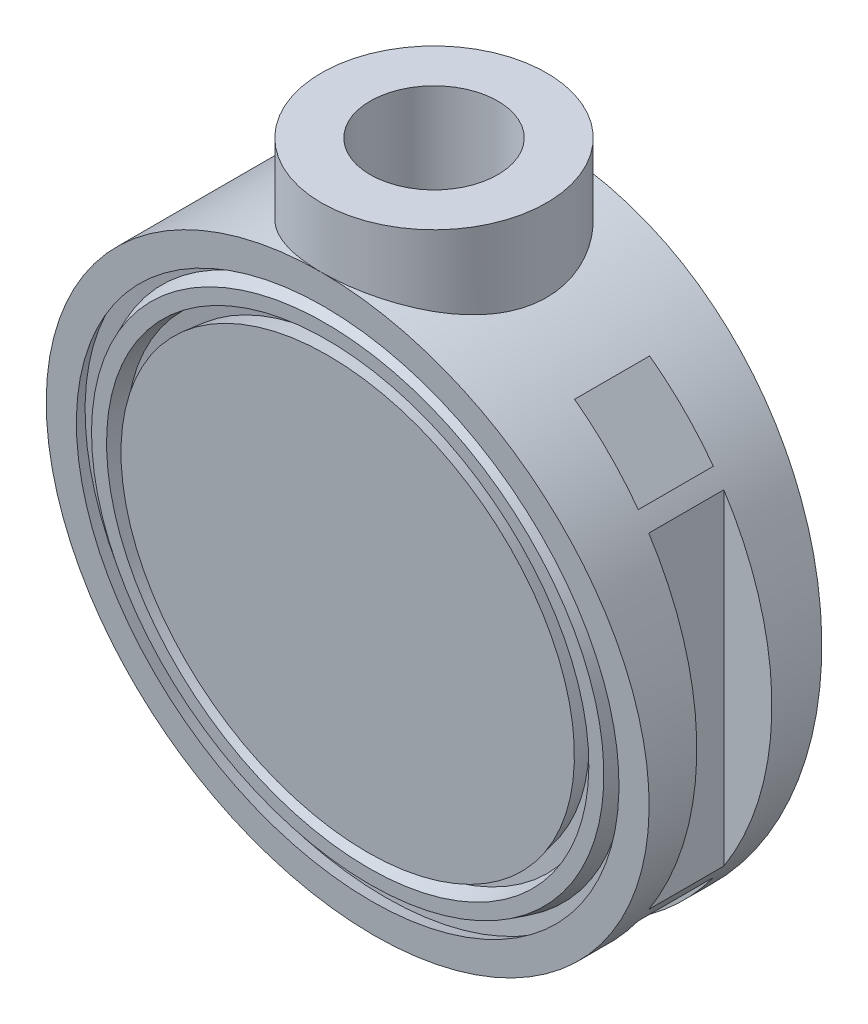
SolidWorks part; units mm, degrees
note: The reader was unsure of these and kept them because the rebuilt part matched: shared geometry of "Sketch3<4>".
ref_plane "Front Plane" through (0, 0, 0) normal (0, 0, 1) x (1, 0, 0)
ref_plane "Top Plane" through (0, 0, 0) normal (0, 1, 0) x (1, 0, 0)
ref_plane "Right Plane" through (0, 0, 0) normal (1, 0, 0) x (0, 0, -1)
sketch "Sketch1" plane through (0, 0, 0) normal (1, 0, 0) x (0, 0, -1)
  line L0 (0, 0) -> (0, 63.5) construction
  line L1 (-23.8125, 63.5) -> (23.8125, 63.5)
  line L2 (23.8125, 63.5) -> (23.8125, 0)
  line L3 (-23.8125, 0) -> (23.8125, 0) construction
  line L4 (-23.8125, 63.5) -> (-23.8125, 0)
  line L5 (-23.8125, 0) -> (23.8125, 0)
  dimension "D1" = 23.8125
  dimension "D2" = 63.5
revolve "Revolve1" add sketch "Sketch1" angle 360 about L5
sketch "Sketch2" plane through (0, 0, 0) normal (1, 0, 0) x (0, 0, -1)
  line L0 (-23.8125, 63.5) -> (-12.7, -63.5)
  line L1 (-23.8125, -63.5) -> (23.8125, -63.5) construction
  line L2 (-12.7, -63.5) -> (0, -63.5)
  line L4 (23.8125, 63.5) -> (-23.8125, 63.5) construction
  line L5 (0, 63.5) -> (0, -63.5) construction
  line L6 (-23.8125, 63.5) -> (-23.8125, -63.5) construction
  line L7 (-23.8125, -63.5) -> (23.8125, -63.5)
  line L8 (-23.8125, 63.5) -> (-23.8125, -63.5)
  line L9 (23.8125, 63.5) -> (23.8125, -63.5)
  line L10 (23.8125, 63.5) -> (12.7, -63.5)
  dimension "D1" = 12.7
extrude "Cut-Extrude1" cut sketch "Sketch2" against normal up to surface and the other way up to surface contours L0 L8 L7 | L9 L10 L7 up to face at (63.5, 0, 23.8125) other way up to face at (63.5, 0, 23.8125)
sketch "Sketch3" plane through (0, 0, 0) normal (1, 0, 0) x (0, 0, -1)
  line L0 (-18.2562, 0) -> (0, 1.5974) construction
  line L1 (-23.8125, 63.5) -> (-12.7, -63.5) construction
  line L2 (-13.2747, -56.9325) -> (-10.2888, -57.7325)
  line L3 (-10.2888, -57.7325) -> (-10.2888, -54.632)
  line L4 (-10.2888, -54.632) -> (-13.5525, -53.7575)
  line L5 (-13.8282, -50.6066) -> (-10.2888, -49.6583)
  line L6 (-10.2888, -49.6583) -> (-10.2888, -46.5577)
  line L7 (-10.2888, -46.5577) -> (-14.0933, -47.5771)
  line L9 (-13.6936, -52.1451) -> (13.6936, -52.1451) construction
  line L11 (12.7, -63.5) -> (23.8125, 63.5) construction
  line L12 (-10.2888, -49.6583) -> (-10.2888, -54.632) construction
  line L13 (0, 1.5974) -> (0, -52.1451) construction
  line L14 (10.2888, -49.6583) -> (10.2888, -54.632) construction
  line L15 (18.2562, 0) -> (0, 1.5974) construction
  line L16 (10.2888, -46.5577) -> (14.0933, -47.5771)
  line L17 (10.2888, -49.6583) -> (10.2888, -46.5577)
  line L18 (13.8282, -50.6066) -> (10.2888, -49.6583)
  line L19 (10.2888, -54.632) -> (13.5525, -53.7575)
  line L20 (10.2888, -57.7325) -> (10.2888, -54.632)
  line L21 (13.2747, -56.9325) -> (10.2888, -57.7325)
  line L22 (12.7, -63.5) -> (23.8125, 63.5)
  line L23 (-23.8125, 63.5) -> (-12.7, -63.5)
  point P11 (-10.2888, -52.1451)
  dimension "D1" = 15
  dimension "D2" = 15
  dimension "D3" = 3.175
  dimension "D4" = 3.175
  dimension "D5" = 57.15
  dimension "D6" = 50.8
revolve "Cut-Revolve1" cut sketch "Sketch3" angle 360 about L0
revolve "Cut-Revolve2" cut sketch "Sketch3<4>" angle 360 about L15
sketch "Sketch3<4>" plane through (0, 0, 0) normal (1, 0, 0) x (0, 0, -1) same geometry as "Sketch3"
sketch "Sketch4" plane through (0, 0, 0) normal (1, 0, 0) x (0, 0, -1)
  line L0 (0, 63.5) -> (0, -63.5) construction
  line L1 (23.8125, 63.5) -> (-23.8125, 63.5) construction
  line L2 (-12.7, -63.5) -> (12.7, -63.5) construction
  line L3 (-6.35, -60.325) -> (-6.35, -46.6674)
  line L4 (-6.35, -46.6674) -> (-7.9375, -45.0799)
  line L5 (-7.9375, -45.0799) -> (-15.6506, 43.0693)
  line L6 (-23.8125, 63.5) -> (-12.7, -63.5) construction
  line L7 (-12.7, -63.5) -> (-9.525, -63.5)
  line L8 (-9.525, -63.5) -> (-6.35, -60.325)
  line L9 (-9.525, -63.5) -> (0, -63.5)
  line L10 (-14.3854, 44.45) -> (-13.4937, 44.45)
  line L11 (-13.4937, 44.45) -> (-13.4937, 76.2)
  line L12 (-13.4937, 76.2) -> (0, 76.2)
  line L13 (0, 76.2) -> (0, 63.5)
  arc A1 (-15.6506, 43.0693) -> (-14.3854, 44.45) centre (-14.3854, 43.18) cw
  point P6 (-6.35, -63.5)
  dimension "D10" = 1.27
  dimension "D1" = 6.35
  dimension "D2" = 6.35
  dimension "D3" = 3.175
  dimension "D4" = 45
  dimension "D5" = 45
  dimension "D6" = 1.5875
  dimension "D7" = 31.75
  dimension "D8" = 13.4937
  dimension "D9" = 76.2
revolve "Cut-Revolve3" cut sketch "Sketch4" angle 360 about L0
ref_plane "Plane1" through (0, 63.5, 0) normal (0, 1, 0) x (1, 0, 0)
sketch "Sketch5" plane through (0, 63.5, 0) normal (0, 1, 0) x (1, 0, 0)
  circle A0 centre (0, 0) radius 23.8125
  circle A1 centre (0, 0) radius 13.4938
  dimension "D1" = 47.625
  dimension "D2" = 26.9875
extrude "Boss-Extrude1" add sketch "Sketch5" along normal blind 12.7 and the other way up to body separate body
sketch "Sketch6" plane through (0, 0, 0) normal (0, 0, 1) x (1, 0, 0)
  line L0 (19.05, 22.225) -> (19.05, -22.225) construction
  line L1 (23.0188, 22.225) -> (23.0188, -22.225)
  line L2 (15.0813, 22.225) -> (15.0813, -22.225)
  line L3 (0, 0) -> (44.9013, 44.9013) construction
  line L4 (0, 0) -> (44.9013, -44.9013) construction
  line L5 (0, 0) -> (58.2067, 0) construction
  line L6 (37.6581, 51.1285) -> (14.313, 27.7834)
  line L7 (7.9375, -45.0799) -> (15.6506, 43.0693) construction
  line L8 (51.1285, 37.6581) -> (44.7449, 31.2746)
  line L9 (37.6581, -51.1285) -> (28.5488, -42.0191)
  line L10 (51.1285, -37.6581) -> (44.7449, -31.2746)
  line L11 (43.815, 8.2422) -> (43.815, -8.2422)
  line L12 (0, 0) -> (58.6664, 24.3004) construction
  line L13 (53.34, 34.4542) -> (53.34, -34.4542)
  line L14 (43.815, -29.0295) -> (43.815, -25.4251)
  line L15 (39.425, 11.1755) -> (36.1125, 9.8034)
  line L16 (32.4675, -18.6034) -> (41.855, -22.4918)
  line L17 (32.4675, 18.6034) -> (41.855, 22.4918)
  line L18 (43.815, 25.4251) -> (43.815, 29.0295)
  line L19 (39.425, -11.1755) -> (36.1125, -9.8034)
  line L20 (6.35, -60.325) -> (6.35, -46.6674) construction
  line L21 (6.35, -46.6674) -> (7.9375, -45.0799) construction
  line L22 (7.9375, -45.0799) -> (14.313, 27.7834)
  line L23 (6.35, -46.6674) -> (7.9375, -45.0799)
  line L24 (6.35, -50.4016) -> (6.35, -46.6674)
  line L25 (37.6581, 51.1285) -> (46.6383, 60.1087)
  line L26 (46.6383, 60.1087) -> (60.1087, 46.6383)
  line L27 (60.1087, 46.6383) -> (51.1285, 37.6581)
  line L28 (51.1285, -37.6581) -> (60.1087, -46.6383)
  line L29 (60.1087, -46.6383) -> (46.6383, -60.1087)
  line L30 (46.6383, -60.1087) -> (37.6581, -51.1285)
  line L31 (14.313, 27.7834) -> (0, 27.7834)
  line L32 (0, 27.7834) -> (0, -50.6066)
  line L33 (0, -50.6066) -> (6.35, -50.4016)
  arc A0 (23.0188, 22.225) -> (15.0813, 22.225) centre (19.05, 22.225) ccw
  arc A1 (15.0813, -22.225) -> (23.0188, -22.225) centre (19.05, -22.225) ccw
  circle A2 centre (0, 0) radius 63.5 construction
  arc A3 (32.4675, 18.6034) -> (36.1125, 9.8034) centre (34.29, 14.2034) ccw
  arc A4 (32.4675, -18.6034) -> (36.1125, -9.8034) centre (34.29, -14.2034) cw
  arc A5 (43.815, -25.4251) -> (41.855, -22.4918) centre (40.64, -25.4251) ccw
  arc A6 (43.815, -8.2422) -> (39.425, -11.1755) centre (40.64, -8.2422) cw
  arc A7 (43.815, 25.4251) -> (41.855, 22.4918) centre (40.64, 25.4251) cw
  arc A8 (39.425, 11.1755) -> (43.815, 8.2422) centre (40.64, 8.2422) cw
  arc A9 (44.7449, 31.2746) -> (43.815, 29.0295) centre (46.99, 29.0295) ccw
  arc A10 (43.815, -29.0295) -> (44.7449, -31.2746) centre (46.99, -29.0295) ccw
  arc A11 (28.5488, -42.0191) -> (6.35, -50.4016) centre (0, 0) cw
  arc A13 (51.1285, -37.6581) -> (51.1285, 37.6581) centre (0, 0) ccw
  ellipse E0 centre (0, 0.2532) end of major axis (-58.2073, 0.2532) minor radius 57.9857 construction
  ellipse E1 centre (0, 0) end of major axis (-50.8, 0) minor radius 50.6066 construction
  point P2 (19.05, 0)
  point P32 (43.815, 0)
  point P41 (43.815, -23.3037)
  point P48 (43.815, -12.9939)
  point P52 (43.815, 23.3037)
  point P55 (43.815, 12.9939)
  dimension "D13" = 9.525
  dimension "D15" = 3.175
  dimension "D16" = 3.175
  dimension "D17" = 12.7
  dimension "D1" = 7.9375
  dimension "D2" = 44.45
  dimension "D3" = 19.05
  dimension "D4" = 45
  dimension "D5" = 45
  dimension "D6" = 19.05
  dimension "D7" = 9.525
  dimension "D8" = 9.525
  dimension "D9" = 9.525
  dimension "D10" = 22.5
  dimension "D11" = 9.525
  dimension "D12" = 9.525
  dimension "D14" = 116.84
  dimension "D18" = 12.7
  dimension "D19" = 12.7
extrude "Cut-Extrude6" cut sketch "Sketch6" against normal mid plane 15.875 contours L32 L33 L24 L23 L22 L31 | A11 L9 L30 L29 L28 L10 A10 L14 A5 L16 A4 L19 A6 L11 A8 L15 A3 L17 A7 L18 A9 L8 L27 L26 L25 L6 L22 L23 L24 A1 L2 A0 L1 | L13 A13
equation "\"hzj\"=1.74046"
